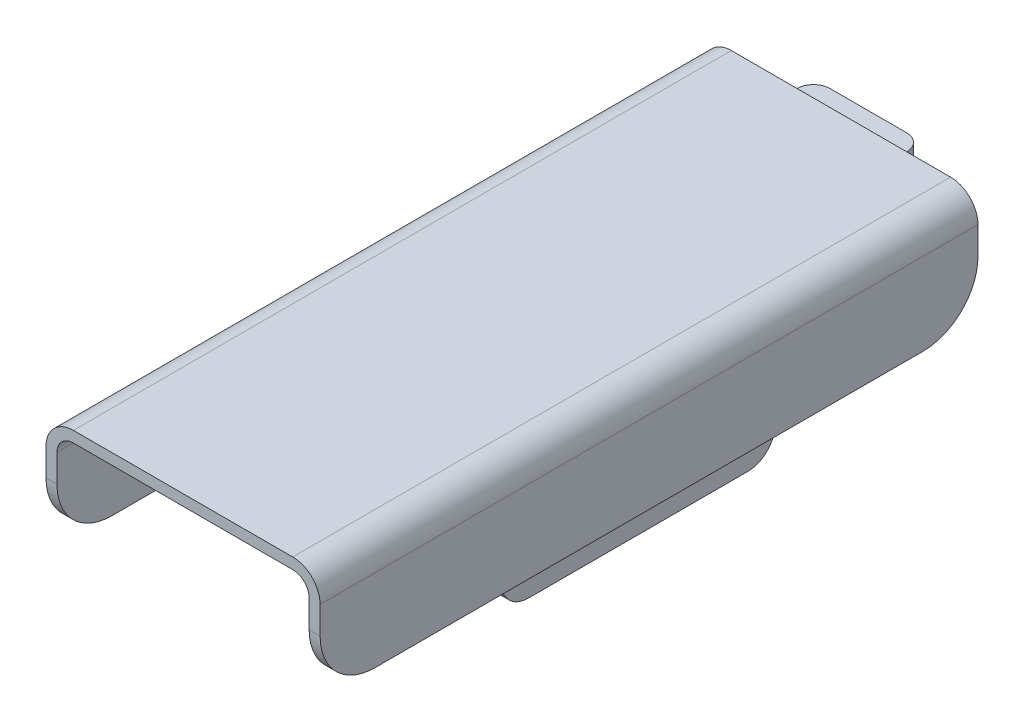
SolidWorks part; units mm, degrees
ref_plane "Front Plane" through (0, 0, 0) normal (0, 0, 1) x (1, 0, 0)
ref_plane "Top Plane" through (0, 0, 0) normal (0, 1, 0) x (1, 0, 0)
ref_plane "Right Plane" through (0, 0, 0) normal (1, 0, 0) x (0, 0, -1)
sketch "Sketch1" plane through (0, 0, 0) normal (0, 0, 1) x (1, 0, 0)
  line L0 (-62.3906, 20.6479) -> (-62.3906, 26.5485) construction
  line L1 (-62.3906, 20.6479) -> (-62.3906, -14.3521) construction
  line L2 (-14.3906, 5.6479) -> (-14.3906, 20.6479)
  line L4 (-17.3906, 23.6479) -> (-57.3906, 23.6479)
  line L5 (-60.3906, 20.6479) -> (-60.3906, 5.6479)
  line L6 (-60.3906, 5.6479) -> (-62.3906, 5.6479)
  line L7 (-14.3906, 5.6479) -> (-12.3906, 5.6479)
  line L16 (-17.3906, 25.6479) -> (-57.3906, 25.6479)
  line L17 (-62.3906, 20.6479) -> (-62.3906, 5.6479)
  line L23 (-12.3906, 5.6479) -> (-12.3906, 20.6479)
  arc A0 (-57.3906, 25.6479) -> (-62.3906, 20.6479) centre (-57.3906, 20.6479) ccw
  arc A1 (-17.3906, 25.6479) -> (-12.3906, 20.6479) centre (-17.3906, 20.6479) cw
  arc A2 (-17.3906, 23.6479) -> (-14.3906, 20.6479) centre (-17.3906, 20.6479) cw
  arc A3 (-57.3906, 23.6479) -> (-60.3906, 20.6479) centre (-57.3906, 20.6479) ccw
  dimension "D4" = 20
  dimension "D1" = 5
  dimension "D2" = 2
  dimension "D3" = 20
extrude "Boss-Extrude1" add sketch "Sketch1" along normal blind 120
fillet "Fillet1" radius 10 4 edges at (-13.3906, 5.6479, 120) (-13.3906, 5.6479, 0) (-61.3906, 5.6479, 0) (-61.3906, 5.6479, 120)
sketch "Sketch2" plane through (0, 5.6479, 0) normal (0, -1, 0) x (1, 0, 0)
  line L0 (-60.3906, 85) -> (-12.3906, 85) construction
  line L1 (-57.3906, 35) -> (-60.3906, 35)
  line L2 (-57.3906, 35) -> (-57.3906, 85)
  line L3 (-57.3906, 85) -> (-60.3906, 85)
  line L4 (-60.3906, 35) -> (-60.3906, 85)
  line L5 (-12.3906, 135.2288) -> (-12.3906, -153) construction
  line L9 (-12.3906, 35) -> (-12.3906, 85) construction
  line L10 (-15.3906, 85) -> (-12.3906, 85) construction
  line L11 (-15.3906, 35) -> (-15.3906, 85) construction
  line L12 (-15.3906, 35) -> (-12.3906, 35) construction
extrude "Boss-Extrude2" add sketch "Sketch2" against normal up to surface and the other way blind 5 up to face at (-59.2012, 22.4586, 60)
sketch "Sketch12" plane through (0, 5.6479, 0) normal (0, -1, 0) x (1, 0, 0)
  line L0 (-37.3906, 120) -> (-37.3906, 0) construction
  line L1 (-57.3906, 120) -> (-17.3906, 120) construction
  line L2 (-57.3906, 0) -> (-17.3906, 0) construction
  line L3 (-14.3906, 35) -> (-17.3906, 35)
  line L4 (-57.3906, 35) -> (-57.3906, 85)
  line L5 (-57.3906, 85) -> (-60.3906, 85)
  line L6 (-60.3906, 85) -> (-60.3906, 35)
  line L7 (-60.3906, 35) -> (-57.3906, 35)
  line L8 (-57.3906, 35) -> (-57.3906, 85) construction
  line L9 (-57.3906, 85) -> (-60.3906, 85) construction
  line L10 (-60.3906, 85) -> (-60.3906, 35) construction
  line L11 (-60.3906, 35) -> (-57.3906, 35) construction
  line L12 (-14.3906, 85) -> (-14.3906, 35)
  line L13 (-17.3906, 85) -> (-14.3906, 85)
  line L14 (-17.3906, 35) -> (-17.3906, 85)
  dimension "D1" = 0
extrude "Boss-Extrude5" add sketch "Sketch12" against normal up to surface and the other way blind 5 up to face at (-15.5799, 22.4586, 60)
sketch "Sketch3" plane through (0, 23.6479, 0) normal (0, -1, 0) x (1, 0, 0)
  line L0 (-37.3906, 0) -> (-37.3906, 120) construction
  line L1 (-27.3906, 10) -> (-47.3906, 10)
  line L2 (-27.3906, 10) -> (-27.3906, -5)
  line L3 (-27.3906, -5) -> (-47.3906, -5)
  line L4 (-47.3906, 10) -> (-47.3906, -5)
  line L6 (-12.3906, 0) -> (-12.3906, 10) construction
  dimension "D1" = 10
  dimension "D2" = 20
  dimension "D3" = 15
  dimension "D4" = 25
extrude "Boss-Extrude3" add sketch "Sketch3" along normal blind 3
fillet "Fillet2" radius 5 4 edges at (-58.8906, 0.6479, 35) (-58.8906, 0.6479, 85) (-15.8906, 0.6479, 85) (-15.8906, 0.6479, 35)
chamfer "Chamfer1" distance 4 angle 45 1 edges at (-37.3906, 23.6479, 10)
fillet "Fillet3" radius 4 2 edges at (-37.3906, 20.6479, 11) (-37.3906, 23.6479, 14)
fillet "Fillet4" radius 3 2 edges at (-47.3906, 22.1479, -5) (-27.3906, 22.1479, -5)
fillet "Fillet5" radius 3 2 edges at (-17.3906, 23.6479, 60) (-57.3906, 23.6479, 60)
